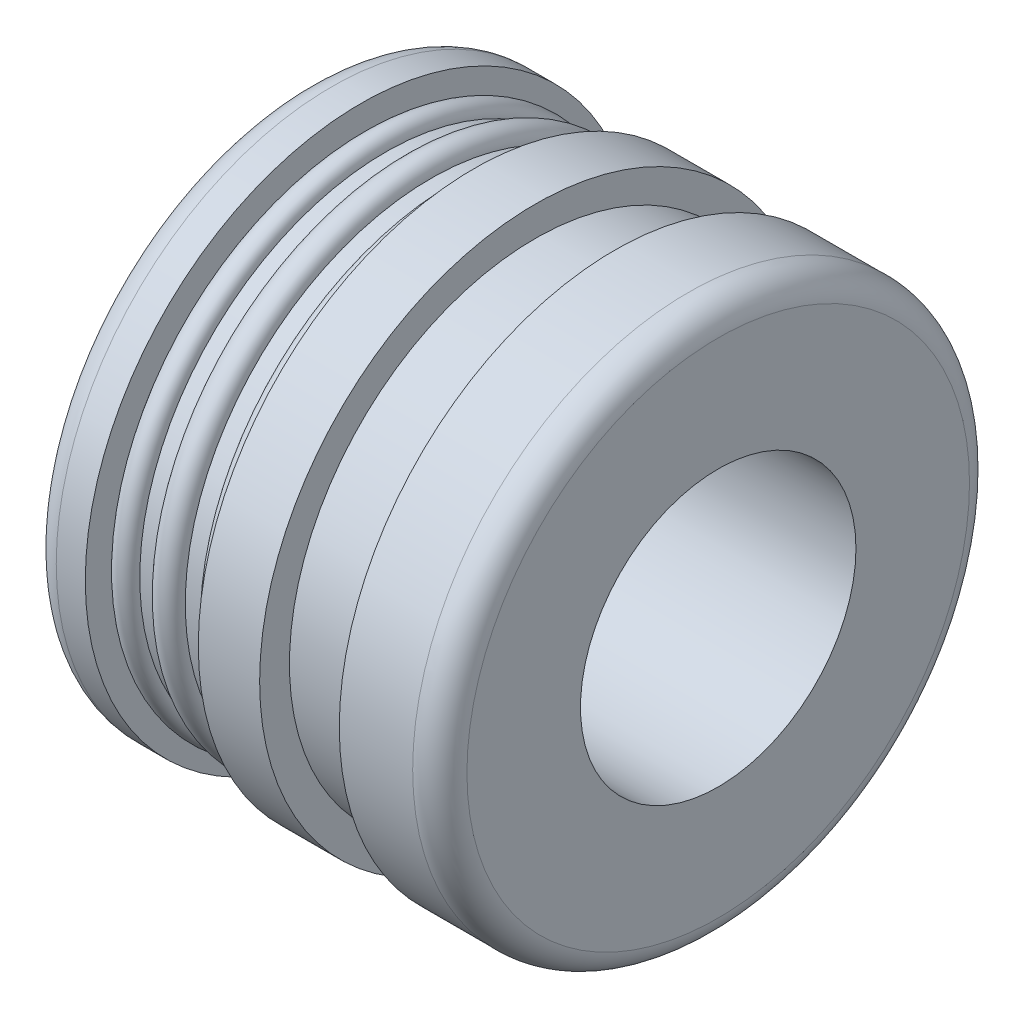
SolidWorks part; units mm, degrees
material "Rubber"
ref_plane "Front Plane" through (0, 0, 0) normal (0, 0, 1) x (1, 0, 0)
ref_plane "Top Plane" through (0, 0, 0) normal (0, 1, 0) x (1, 0, 0)
ref_plane "Right Plane" through (0, 0, 0) normal (1, 0, 0) x (0, 0, -1)
sketch "Sketch1" plane through (0, 0, 0) normal (0, 0, 1) x (1, 0, 0)
  line L5 (-7.7391, 12.7) -> (-9.0786, 12.7)
  line L8 (3.9688, 12.7) -> (3.9688, 11.3266)
  line L9 (3.9688, 11.3266) -> (0.2977, 11.3266)
  line L10 (0.2977, 11.3266) -> (0.2977, 12.7)
  line L11 (0.2977, 12.7) -> (-2.5301, 12.7)
  line L12 (-2.5301, 12.7) -> (-2.5301, 11.3266)
  line L13 (-2.5301, 11.3266) -> (-2.5741, 11.3266)
  line L14 (-7.7391, 11.3266) -> (-7.7391, 12.7)
  line L15 (-7.7391, 12.7) -> (-9.0786, 12.7)
  line L16 (-10.3124, 6.35) -> (-10.3124, 11.3266)
  line L17 (0.2977, 12.7) -> (-2.5301, 12.7)
  line L18 (8.7376, 11.5839) -> (8.7376, 6.35)
  line L19 (8.7376, 6.35) -> (-10.3124, 6.35)
  line L20 (0, 0) -> (-2.9205, 0)
  line L21 (-5.7649, 11.3266) -> (-6.6016, 11.3266)
  line L22 (-3.5983, 11.3266) -> (-4.5043, 11.3266)
  line L23 (-7.6802, 11.3266) -> (-7.7391, 11.3266)
  line L24 (7.353, 12.7) -> (3.9688, 12.7)
  arc A1 (-10.3124, 11.3266) -> (-9.0786, 12.7) centre (-9.0088, 11.3964) cw
  arc A2 (8.7376, 11.5839) -> (7.353, 12.7) centre (7.4873, 11.4497) ccw
  arc A3 (-2.5741, 11.3266) -> (-3.5983, 11.3266) centre (-3.0862, 11.3266) ccw
  arc A4 (-4.5043, 11.3266) -> (-5.7649, 11.3266) centre (-5.1346, 11.3266) ccw
  arc A5 (-6.6016, 11.3266) -> (-7.6802, 11.3266) centre (-7.1409, 11.3266) ccw
  point P0 (0, 0)
revolve "Revolve1" add sketch "Sketch1" angle 360 about L20 region at (-0.6946, 9.2579, 0)
